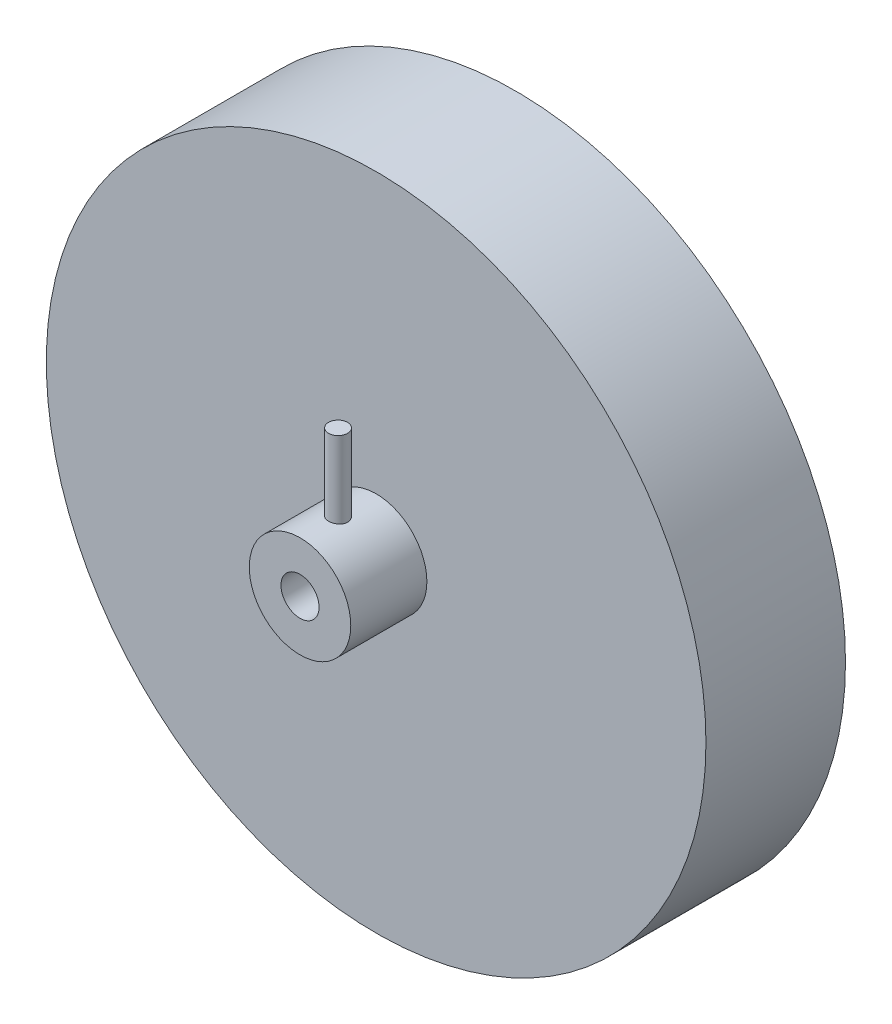
SolidWorks part; units mm, degrees
ref_plane "Front Plane" through (0, 0, 0) normal (0, 0, 1) x (1, 0, 0)
ref_plane "Top Plane" through (0, 0, 0) normal (0, 1, 0) x (1, 0, 0)
ref_plane "Right Plane" through (0, 0, 0) normal (1, 0, 0) x (0, 0, -1)
sketch "Sketch1" plane through (0, 0, 0) normal (0, 0, 1) x (1, 0, 0)
  circle A0 centre (0, 0) radius 52
  dimension "D1" = 104
extrude "Boss-Extrude1" add sketch "Sketch1" along normal mid plane 22
sketch "Sketch2" plane through (0, 0, 11) normal (0, 0, 1) x (1, 0, 0)
  circle A0 centre (0, 0) radius 8
  dimension "D1" = 16
extrude "Boss-Extrude2" add sketch "Sketch2" along normal blind 12
sketch "Sketch3" plane through (0, 0, 0) normal (0, 1, 0) x (1, 0, 0)
  line L1 (8, -23) -> (8, -11) construction
  line L3 (-8, -17) -> (8, -17) construction
  line L4 (-8, -11) -> (-8, -23) construction
  line L5 (0, -22.2086) -> (0, 0) construction
  circle A0 centre (0, -17) radius 1.5
  dimension "D1" = 3
extrude "Boss-Extrude3" add sketch "Sketch3" along normal blind 20
sketch "Sketch4" plane through (0, 0, 23) normal (0, 0, -1) x (-1, 0, 0)
  circle A0 centre (0, 0) radius 3
  dimension "D1" = 6
extrude "Cut-Extrude3" cut sketch "Sketch4" along normal blind 12
